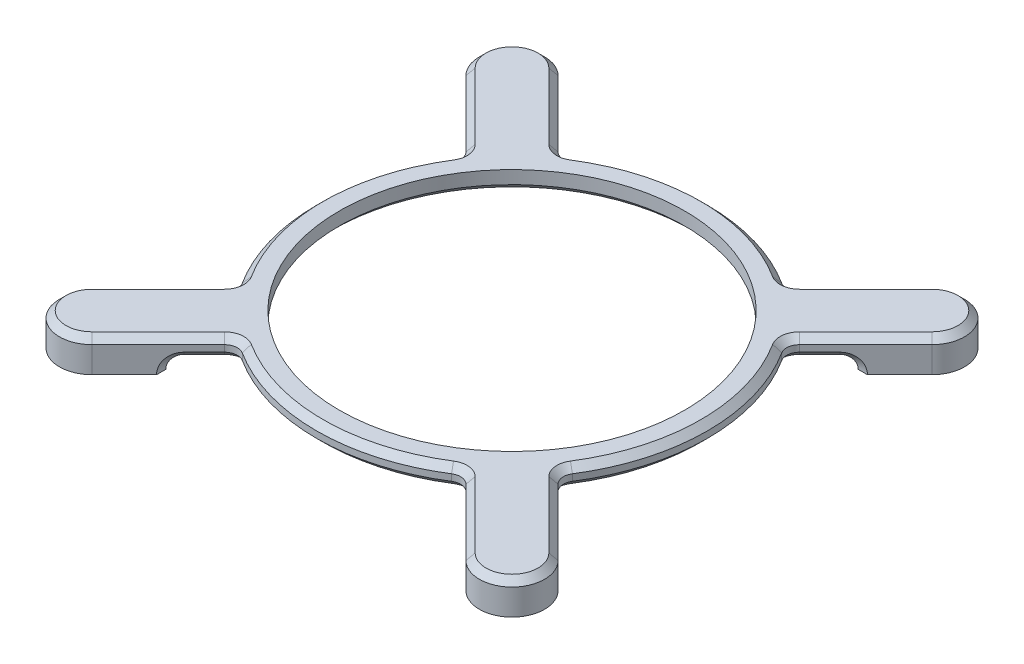
SolidWorks part; units mm, degrees
ref_plane "Front Plane" through (0, 0, 0) normal (0, 0, 1) x (1, 0, 0)
ref_plane "Top Plane" through (0, 0, 0) normal (0, 1, 0) x (1, 0, 0)
ref_plane "Right Plane" through (0, 0, 0) normal (1, 0, 0) x (0, 0, -1)
sketch "Base" plane through (0, 0, 0) normal (0, 1, 0) x (1, 0, 0)
  line L0 (0, 0) -> (20.0512, 0) construction
  line L1 (0, 0) -> (0, -11.6602) construction
  line L2 (0, 0) -> (-32.2302, 32.2302) construction
  line L3 (-26.913, 15.5134) -> (-32.4976, 9.9288) construction
  line L4 (-35.7657, 28.6947) -> (-28.6947, 35.7657) construction
  line L5 (-28.6947, 35.7657) -> (-17.381, 24.452)
  line L6 (-35.7657, 28.6947) -> (-24.452, 17.381)
  line L7 (-30.1089, 23.0378) -> (-23.0378, 30.1089)
  line L8 (35.7657, 28.6947) -> (24.452, 17.381)
  line L9 (28.6947, 35.7657) -> (17.381, 24.452)
  line L10 (23.0378, 30.1089) -> (30.1089, 23.0378)
  line L11 (28.6947, 35.7657) -> (35.7657, 28.6947) construction
  line L12 (0, 0) -> (32.2302, 32.2302) construction
  line L13 (28.6947, -35.7657) -> (17.381, -24.452)
  line L14 (35.7657, -28.6947) -> (24.452, -17.381)
  line L15 (30.1089, -23.0378) -> (23.0378, -30.1089)
  line L16 (35.7657, -28.6947) -> (28.6947, -35.7657) construction
  line L17 (0, 0) -> (32.2302, -32.2302) construction
  line L18 (-35.7657, -28.6947) -> (-24.452, -17.381)
  line L19 (-28.6947, -35.7657) -> (-17.381, -24.452)
  line L20 (-23.0378, -30.1089) -> (-30.1089, -23.0378)
  line L21 (-28.6947, -35.7657) -> (-35.7657, -28.6947) construction
  line L22 (0, 0) -> (-32.2302, -32.2302) construction
  circle A0 centre (0, 0) radius 26.5 construction
  circle A1 centre (0, 0) radius 30
  circle A2 centre (0, 0) radius 26.5
  circle A3 centre (-32.2302, 32.2302) radius 3.05
  arc A4 (-35.7657, 28.6947) -> (-28.6947, 35.7657) centre (-32.2302, 32.2302) cw
  circle A6 centre (32.2302, 32.2302) radius 3.05
  arc A7 (28.6947, 35.7657) -> (35.7657, 28.6947) centre (32.2302, 32.2302) cw
  circle A9 centre (32.2302, -32.2302) radius 3.05
  arc A10 (35.7657, -28.6947) -> (28.6947, -35.7657) centre (32.2302, -32.2302) cw
  circle A12 centre (-32.2302, -32.2302) radius 3.05
  arc A13 (-28.6947, -35.7657) -> (-35.7657, -28.6947) centre (-32.2302, -32.2302) cw
  point P13 (-21.2132, 21.2132)
  point P28 (21.2132, 21.2132)
  point P38 (21.2132, -21.2132)
  point P48 (-21.2132, -21.2132)
  point P56 (0, 0)
  dimension "D1" = 53
  dimension "D5" = 6.1
  dimension "D7" = 5
  dimension "D4" = 45
  dimension "D8" = 16
  dimension "D2" = 3.5
  dimension "D3" = 0
  dimension "D9" = 4
extrude "Boss-Extrude1" add sketch "Base" along normal blind 2 contours A13 L19 L20 L18 A12 | A10 L14 L15 L13 A9 | A7 L9 L10 L8 A6 | A4 L6 L7 L5 A3 | A6 | A3 | A12 | A9 region at (-26.0082, 0, -32.7954) region at (26.0082, 0, -32.7954) region at (-26.7153, 0, 26.7153) region at (32.7954, 0, 26.0082) region at (-32.2302, 0, -32.2302) region at (32.2302, 0, -32.2302) region at (32.2302, 0, 32.2302) region at (-32.2302, 0, 32.2302)
extrude "Boss-Extrude2" add sketch "Base<3>" along normal blind 3 from surface contours A1 A2 | A1 L18 L20 L19 | A13 L19 L20 L18 A12 | A1 L13 L15 L14 | A10 L14 L15 L13 A9 | A1 L8 L10 L9 | A7 L9 L10 L8 A6 | A1 L5 L7 L6 | A4 L6 L7 L5 A3 | A3 | A12 | A9 | A6 region at (-26.0082, 0, -32.7954) region at (-23.8433, 0, -23.8433) region at (0, 0, -29.1515) region at (23.8433, 0, -23.8433) region at (26.0082, 0, -32.7954) region at (-23.8433, 0, 23.8433) region at (-26.7153, 0, 26.7153) region at (23.8433, 0, 23.8433) region at (32.7954, 0, 26.0082) region at (-32.2302, 0, -32.2302) region at (32.2302, 0, -32.2302) region at (32.2302, 0, 32.2302) region at (-32.2302, 0, 32.2302) starting at face at (-30.2857, 2, 30.2857)
sketch "Base<3>" plane through (0, 0, 0) normal (0, 1, 0) x (1, 0, 0) same geometry as "Base"
fillet "Fillet1" radius 2 12 edges at (-17.381, 3.5, -24.452) (24.452, 3.5, -17.381) (24.452, 3.5, 17.381) (17.381, 3.5, -24.452) (-17.381, 3.5, 24.452) (-24.452, 3.5, 17.381) (-24.452, 3.5, -17.381) (17.381, 3.5, 24.452) (-26.5734, 2, 26.5734) (-26.5734, 2, -26.5734) (26.5734, 2, 26.5734) (26.5734, 2, -26.5734)
chamfer "Chamfer1" distance 1 angle 45 53 edges at (29.6947, 1.4142, 22.6236) (29.6947, 1.4142, -22.6236) (27.1548, 2, 20.0837) (25.0413, 2, 17.3497) (30, 2, 0) (25.0413, 2, -17.3497) (27.1548, 2, -20.0837) (22.6236, 1.4142, -29.6947) (-22.6236, 1.4142, -29.6947) (20.0837, 2, -27.1548) (17.3497, 2, -25.0413) (0, 2, -30) (-17.3497, 2, -25.0413) (-20.0837, 2, -27.1548) (-29.6947, 1.4142, -22.6236) (-29.6947, 1.4142, 22.6236) (-27.1548, 2, -20.0837) (-25.0413, 2, -17.3497) (-30, 2, 0) (-25.0413, 2, 17.3497) (-27.1548, 2, 20.0837) (22.6236, 1.4142, 29.6947) (-22.6236, 1.4142, 29.6947) (20.0837, 2, 27.1548) (17.3497, 2, 25.0413) (0, 2, 30) (-17.3497, 2, 25.0413) (-20.0837, 2, 27.1548) (0, 2, 26.5) (35.7657, 5, 35.7657) (30.6903, 5, 23.6193) (23.6193, 5, 30.6903) (25.0413, 5, 17.3497) (17.3497, 5, 25.0413) (30, 5, 0) (0, 5, 30) (25.0413, 5, -17.3497) (-17.3497, 5, 25.0413) (30.6903, 5, -23.6193) (-23.6193, 5, 30.6903) (35.7657, 5, -35.7657) (-35.7657, 5, 35.7657) (23.6193, 5, -30.6903) (-30.6903, 5, 23.6193) (17.3497, 5, -25.0413) (-25.0413, 5, 17.3497) (0, 5, -30) (-30, 5, 0) (-17.3497, 5, -25.0413) (-25.0413, 5, -17.3497) (-23.6193, 5, -30.6903) (-30.6903, 5, -23.6193) (-35.7657, 5, -35.7657)
extrude "Cut-Extrude1" cut sketch "Base<4>" along normal blind 3.5 contours A9 | A12 | A3 | A6 region at (-32.2302, 0, -32.2302) region at (32.2302, 0, -32.2302) region at (32.2302, 0, 32.2302) region at (-32.2302, 0, 32.2302)
sketch "Base<4>" plane through (0, 0, 0) normal (0, 1, 0) x (1, 0, 0) same geometry as "Base"
equation "\"Radius\"= 53"
equation "\"D8@Base\"=(\"Radius\" + \"Outer_Thickness\")*-1 + 72.5"
equation "\"D1@Base\"=\"Radius\""
equation "\"D3@Base\"=0"
equation "\"Outer_Thickness\"= 3.5"
equation "\"D2@Base\"=\"Outer_Thickness\""
